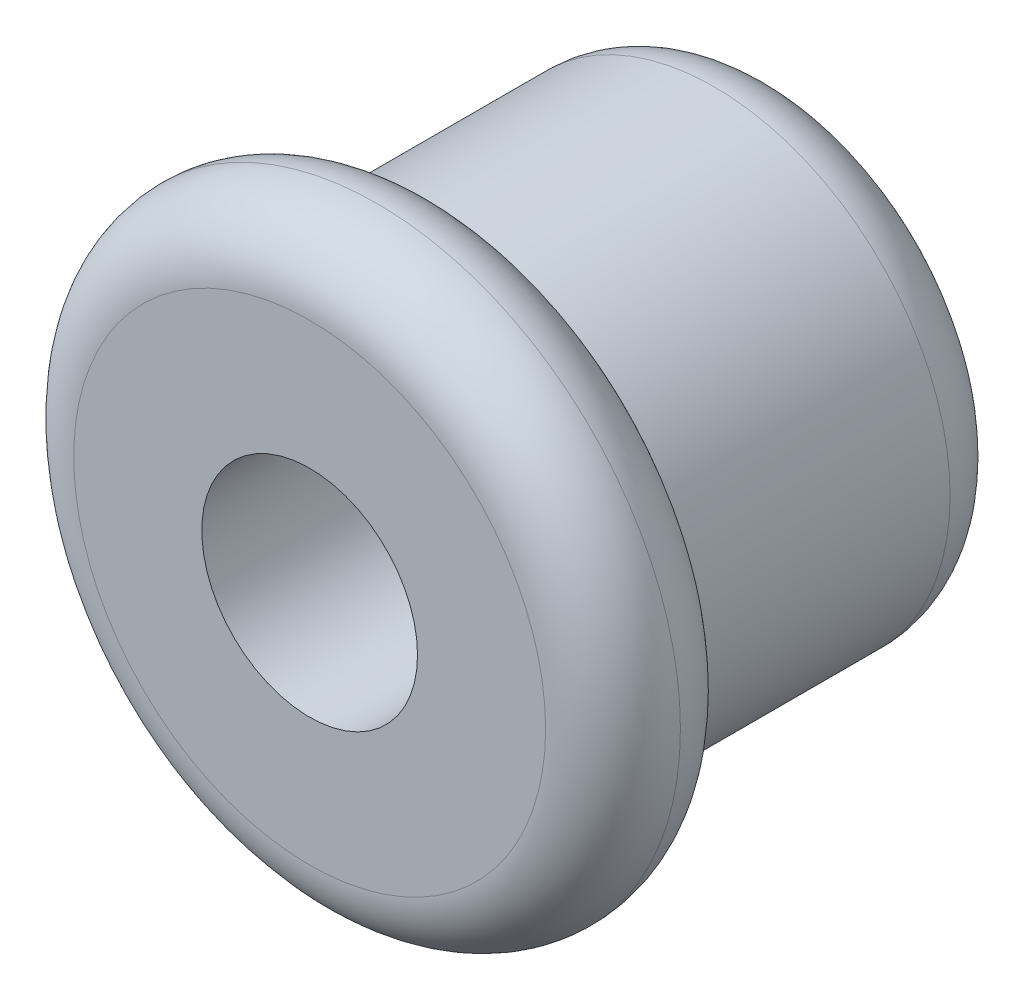
SolidWorks part; units mm, degrees
material "陶瓷"
ref_plane "前视基准面" through (0, 0, 0) normal (0, 0, 1) x (1, 0, 0)
ref_plane "上视基准面" through (0, 0, 0) normal (0, 1, 0) x (1, 0, 0)
ref_plane "右视基准面" through (0, 0, 0) normal (1, 0, 0) x (0, 0, -1)
sketch "草图1" plane through (0, 0, 0) normal (0, 0, 1) x (1, 0, 0)
  circle A0 centre (0, 0) radius 1.75
  dimension "D1" = 3.5
extrude "凸台-拉伸1" add sketch "草图1" along normal blind 2.5
sketch "草图2" plane through (0, 0, 2.5) normal (0, 0, 1) x (1, 0, 0)
  circle A0 centre (0, 0) radius 2.25
  dimension "D1" = 4.5
extrude "凸台-拉伸2" add sketch "草图2" along normal blind 1
sketch "草图3" plane through (0, 0, 3.5) normal (0, 0, 1) x (1, 0, 0)
  circle A0 centre (0, 0) radius 0.8
  dimension "D1" = 1.6
extrude "切除-拉伸1" cut sketch "草图3" against normal through all both and the other way through all
fillet "圆角2" radius 0.5 3 edges at (1.75, 0, 0) (2.25, 0, 2.5) (2.25, 0, 3.5)
